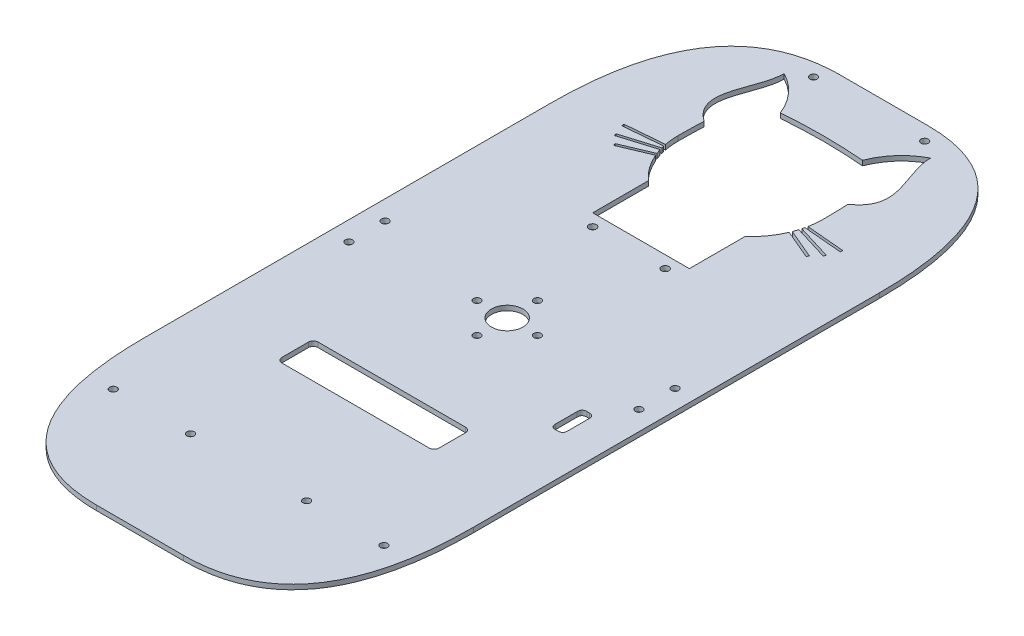
SolidWorks part; units mm, degrees
ref_plane "Спереди" through (0, 0, 0) normal (0, 0, 1) x (1, 0, 0)
ref_plane "Сверху" through (0, 0, 0) normal (0, 1, 0) x (1, 0, 0)
ref_plane "Справа" through (0, 0, 0) normal (1, 0, 0) x (0, 0, -1)
sketch "Эскиз1" plane through (0, 0, 0) normal (0, 1, 0) x (1, 0, 0)
  line L0 (0, 143) -> (0, -165) construction
  line L1 (-68, 143) -> (68, 143)
  line L2 (-68, 143) -> (-68, -165)
  line L3 (-68, -165) -> (68, -165)
  line L4 (68, 143) -> (68, -165)
  line L5 (-68, 0) -> (68, 0) construction
  dimension "D1" = 136
  dimension "D2" = 143
  dimension "D3" = 165
extrude "тело" add sketch "Эскиз1" along normal blind 2
sketch "Эскиз12" plane through (0, 2, 0) normal (0, 1, 0) x (1, 0, 0)
  line L0 (0, 143) -> (0, -165) construction
  line L1 (68, 143) -> (-68, 143) construction
  line L2 (-68, -165) -> (68, -165) construction
  line L3 (60, -3.5) -> (60, -18.5) construction
  line L4 (60, -11) -> (-60, -11) construction
  line L5 (-60, -3.5) -> (-60, -18.5) construction
  circle A0 centre (60, -3.5) radius 1.5
  circle A1 centre (-60, -3.5) radius 1.5
  circle A2 centre (-60, -18.5) radius 1.5
  circle A3 centre (60, -18.5) radius 1.5
  point P12 (-60, -11)
  point P17 (0, -11)
  point P19 (0, -11)
  dimension "D2" = 3
  dimension "D1" = 15
  dimension "D3" = 60
extrude "крепление подвески" cut sketch "Эскиз12" against normal through all
sketch "Эскиз8" plane through (0, 2, 0) normal (0, 1, 0) x (1, 0, 0)
  line L0 (-20, -130) -> (20, -130) construction
  line L1 (0, -165) -> (0, 143) construction
  line L2 (-68, -165) -> (68, -165) construction
  line L3 (68, 143) -> (-68, 143) construction
  circle A0 centre (-20, -130) radius 1.5
  circle A1 centre (20, -130) radius 1.5
  point P10 (0, -130)
  dimension "D1" = 3
  dimension "D2" = 40
  dimension "D3" = 130
extrude "крепление камеры" [suppressed] cut sketch "Эскиз8" against normal through all and the other way through all
sketch "Эскиз13" plane through (0, 2, 0) normal (0, 1, 0) x (1, 0, 0)
  line L0 (0, 143) -> (0, -165) construction
  line L1 (68, 143) -> (-68, 143) construction
  line L2 (-68, -165) -> (68, -165) construction
  line L3 (-57, 99) -> (57, 99) construction
  line L4 (-68, -11) -> (68, -11) construction
  line L5 (-57, -36) -> (57, -36) construction
  line L6 (-68, 143) -> (-68, -165) construction
  line L7 (-57, -111) -> (57, -111) construction
  line L8 (68, -165) -> (68, 143) construction
  line L9 (-25, 99) -> (-57, 99) construction
  line L10 (25, 99) -> (57, 99) construction
  line L11 (-57, -36) -> (-25, -36) construction
  line L12 (25, -36) -> (57, -36) construction
  line L13 (-57, -111) -> (-25, -111) construction
  line L14 (25, -111) -> (57, -111) construction
  circle A0 centre (-57, 99) radius 1.5
  circle A1 centre (57, 99) radius 1.5
  circle A2 centre (57, -36) radius 1.5
  circle A3 centre (-57, -36) radius 1.5
  circle A4 centre (-57, -111) radius 1.5
  circle A5 centre (57, -111) radius 1.5
  circle A6 centre (-25, 99) radius 1.5
  circle A7 centre (25, 99) radius 1.5
  circle A8 centre (25, -36) radius 1.5
  circle A9 centre (-25, -36) radius 1.5
  circle A10 centre (-25, -111) radius 1.5
  circle A11 centre (25, -111) radius 1.5
  point P18 (0, 99)
  point P19 (0, -36)
  point P20 (0, -111)
  point P27 (0, -11)
  dimension "D1" = 3
  dimension "D2" = 110
  dimension "D3" = 25
  dimension "D4" = 100
  dimension "D5" = 114
  dimension "D6" = 32
  dimension "D7" = 32
  dimension "D8" = 32
  dimension "D9" = 32
  dimension "D10" = 32
  dimension "D11" = 32
extrude "крепления уголков" [suppressed] cut sketch "Эскиз13" against normal through all
sketch "Эскиз9" plane through (0, 2, 0) normal (0, 1, 0) x (1, 0, 0)
  line L0 (0, -50) -> (0, 50) construction
  line L2 (-68, -165) -> (68, -165) construction
  circle A0 centre (0, -13) radius 6.5
  circle A1 centre (0, -13) radius 12.5 construction
  circle A2 centre (0, -0.5) radius 1.5
  circle A3 centre (12.5, -13) radius 1.5
  circle A4 centre (-12.5, -13) radius 1.5
  circle A5 centre (0, -25.5) radius 1.5
  dimension "D2" = 13
  dimension "D3" = 25
  dimension "D4" = 3
  dimension "D1" = 152
extrude "ось вращения качалки" cut sketch "Эскиз9" against normal through all
sketch "Эскиз5" plane through (0, 2, 0) normal (0, 1, 0) x (1, 0, 0)
  line L0 (-50, -100) -> (50, -60) construction
  line L1 (-50, -60) -> (50, -60) construction
  line L2 (-50, -60) -> (-50, -100) construction
  line L3 (-50, -100) -> (50, -100) construction
  line L4 (50, -60) -> (50, -100) construction
  line L5 (-50, -60) -> (50, -100) construction
  line L6 (-68, -165) -> (68, -165) construction
  circle A0 centre (-50, -60) radius 1.5
  circle A1 centre (50, -60) radius 1.5
  circle A2 centre (50, -100) radius 1.5
  circle A3 centre (-50, -100) radius 1.5
  point P12 (0, -80)
  dimension "D1" = 3
  dimension "D2" = 100
  dimension "D3" = 40
  dimension "D4" = 65
extrude "крепление raspberry" [suppressed] cut sketch "Эскиз5" against normal through all
sketch "Эскиз11" plane through (0, 2, 0) normal (0, 1, 0) x (1, 0, 0)
  line L0 (-32.5, -68.2307) -> (32.5, -68.2307) construction
  line L1 (-32.5, -60.7307) -> (32.5, -60.7307)
  line L2 (-32.5, -60.7307) -> (-32.5, -75.7307)
  line L3 (-32.5, -75.7307) -> (32.5, -75.7307)
  line L4 (32.5, -60.7307) -> (32.5, -75.7307)
  point P11 (0, -60.7307)
  dimension "D1" = 65
  dimension "D2" = 15
extrude "отверстие под провода на нижний этаж" cut sketch "Эскиз11" against normal through all
fillet "Скругление3" radius 2 4 edges at (-32.5, 1, 75.7307) (32.5, 1, 75.7307) (32.5, 1, 60.7307) (-32.5, 1, 60.7307)
sketch "Эскиз14" [suppressed] plane through (0, 2, 0) normal (0, 1, 0) x (1, 0, 0)
  line L0 (0, 160) -> (0, -130) construction
  line L1 (68, 160) -> (-68, 160) construction
  line L2 (-68, -130) -> (68, -130) construction
  line L3 (-47.5, -125) -> (47.5, -125) construction
  line L4 (47.5, -115) -> (47.5, -135) construction
  line L5 (-12.5, -95) -> (12.5, -95) construction
  line L6 (-47.5, -115) -> (-47.5, -135) construction
  circle A0 centre (-47.5, -115) radius 1.5
  circle A1 centre (-47.5, -135) radius 1.5
  circle A2 centre (47.5, -115) radius 1.5
  circle A3 centre (47.5, -135) radius 1.5
  point P8 (0, -125)
  point P14 (-47.5, -125)
  point P15 (47.5, -125)
  dimension "D1" = 3
  dimension "D2" = 20
  dimension "D3" = 30
  dimension "D4" = 95
extrude "крепление стопоров" [suppressed] cut sketch "Эскиз14" against normal through all
sketch "Эскиз15" plane through (0, 2, 0) normal (0, 1, 0) x (1, 0, 0)
  line L0 (-23, 136.75) -> (23, 136.75) construction
  line L1 (68, 143) -> (-68, 143) construction
  circle A0 centre (23, 136.75) radius 1.5
  circle A1 centre (-23, 136.75) radius 1.5
  point P6 (0, 136.75)
  dimension "D1" = 3
  dimension "D2" = 6.25
  dimension "D3" = 46
extrude "Крепление фронтальной камеры" cut sketch "Эскиз15" against normal up to next
sketch "Эскиз16" plane through (0, 2, 0) normal (0, 1, 0) x (1, 0, 0)
  line L0 (-56, -120) -> (-24, -120) construction
  line L1 (-68, -165) -> (68, -165) construction
  line L2 (-68, 143) -> (-68, -165) construction
  line L3 (0, -165) -> (0, 143) construction
  line L4 (68, 143) -> (-68, 143) construction
  circle A0 centre (-56, -120) radius 1.5
  circle A1 centre (-24, -120) radius 1.5
  circle A2 centre (24, -120) radius 1.5
  circle A3 centre (56, -120) radius 1.5
  dimension "D1" = 32
  dimension "D4" = 3
  dimension "D2" = 45
  dimension "D3" = 12
extrude "Крепление силовых уголков со стороны буллета" cut sketch "Эскиз16" against normal up to next
sketch "Эскиз17" plane through (0, 2, 0) normal (0, 1, 0) x (1, 0, 0)
  line L1 (48, -30) -> (53, -30)
  line L2 (48, -30) -> (48, -43)
  line L3 (48, -43) -> (53, -43)
  line L4 (53, -30) -> (53, -43)
  dimension "D2" = 13
  dimension "D3" = 5
extrude "Отверстие по дпитание сервоприводов и шилда" cut sketch "Эскиз17" against normal up to next
sketch "Эскиз18" plane through (0, 2, 0) normal (0, 1, 0) x (1, 0, 0)
  line L0 (0, 0) -> (0, 143) construction
  line L1 (68, 143) -> (-68, 143) construction
  line L2 (-20, 42.3884) -> (20, 42.3884)
  line L3 (20, 42.3884) -> (20, 65.3884)
  line L5 (-20, 65.3884) -> (-20, 42.3884)
  line L6 (10, 42.3884) -> (10, 27.3884)
  line L7 (10, 27.3884) -> (-10, 27.3884)
  line L8 (-10, 27.3884) -> (-10, 42.3884)
  line L9 (28.2843, 77.7491) -> (-28.2843, 77.7491)
  line L11 (-29.2321, 81.0049) -> (-45.2082, 79.623)
  line L12 (15, 37.3884) -> (-15, 37.3884) construction
  line L13 (-28.6978, 79.0063) -> (-43.2061, 74.5863)
  line L16 (-27.6267, 76.0544) -> (-39.8248, 70.8909)
  line L17 (-29.4421, 81.9904) -> (-45.2944, 80.6193)
  line L18 (-28.9733, 79.9677) -> (-43.4975, 75.5429)
  line L19 (-28.0012, 76.9818) -> (-40.2146, 71.8117)
  line L20 (-45.2944, 80.6193) -> (-45.2082, 79.623)
  line L21 (-43.4975, 75.5429) -> (-43.2061, 74.5863)
  line L22 (-40.2146, 71.8117) -> (-39.8248, 70.8909)
  line L23 (-29.3183, 82.0011) -> (-45.2944, 80.6193) construction
  line L24 (-28.6818, 79.0111) -> (-43.2061, 74.5863) construction
  line L25 (-27.6114, 76.0609) -> (-39.8248, 70.8909) construction
  line L26 (40.2146, 71.8117) -> (39.8248, 70.8909)
  line L27 (43.4975, 75.5429) -> (43.2061, 74.5863)
  line L28 (45.2944, 80.6193) -> (45.2082, 79.623)
  line L29 (28.0012, 76.9818) -> (40.2146, 71.8117)
  line L30 (28.9733, 79.9677) -> (43.4975, 75.5429)
  line L31 (29.4421, 81.9904) -> (45.2944, 80.6193)
  line L32 (27.6267, 76.0544) -> (39.8248, 70.8909)
  line L33 (28.6978, 79.0063) -> (43.2061, 74.5863)
  line L34 (29.2321, 81.0049) -> (45.2082, 79.623)
  arc A0 (20, 65.3884) -> (-20, 65.3884) centre (0, 87.7491) ccw construction
  circle A1 centre (15, 37.3884) radius 1.55
  circle A2 centre (-15, 37.3884) radius 1.55
  arc A4 (-30, 87.7491) -> (-28.2843, 115.7491) centre (199.3322, 87.7491) cw
  arc A5 (-28.2843, 115.7491) -> (28.2843, 115.7491) centre (0, -83.2509) cw
  arc A6 (28.2843, 115.7491) -> (30, 87.7491) centre (-199.3322, 87.7491) cw
  arc A7 (-20, 65.3884) -> (-27.6267, 76.0544) centre (0, 87.7491) cw
  arc A8 (20, 65.3884) -> (27.6267, 76.0544) centre (0, 87.7491) ccw
  arc A9 (29.4421, 81.9904) -> (30, 87.7491) centre (0, 87.7491) ccw
  arc A10 (-30.2864, 131.9093) -> (-16.9975, 117.0291) centre (-43.1419, 107.0545) cw
  arc A11 (30.2864, 131.9093) -> (16.9975, 117.0291) centre (43.1419, 107.0545) ccw
  arc A12 (28.9733, 79.9677) -> (29.2321, 81.0049) centre (0, 87.7491) ccw
  arc A13 (28.0012, 76.9818) -> (28.6978, 79.0063) centre (0, 87.7491) ccw
  arc A14 (-28.0012, 76.9818) -> (-28.6978, 79.0063) centre (0, 87.7491) cw
  arc A15 (-28.9733, 79.9677) -> (-29.2321, 81.0049) centre (0, 87.7491) cw
  arc A16 (-29.4421, 81.9904) -> (-30, 87.7491) centre (0, 87.7491) cw
  spline S0 degree 3 poles (-29.7583, 98.2745) (-43.0929, 107.4905) (-30.2542, 120.6232) (-30.2864, 131.9093) knots 0 0 0 0 1 1 1 1
  spline S1 degree 3 poles (29.7583, 98.2745) (43.0929, 107.4905) (30.2542, 120.6232) (30.2864, 131.9093) knots 0 0 0 0 1 1 1 1
  point P9 (0, 27.3884)
  point P15 (0, 42.3884)
  point P25 (0, 37.3884)
  dimension "D6" = 60
  dimension "D8" = 3.1
  dimension "D1" = 40
  dimension "D2" = 20
  dimension "D3" = 15
  dimension "D4" = 23
  dimension "D5" = 10
  dimension "D7" = 12
  dimension "D9" = 5
  dimension "D10" = 30
  dimension "D11" = 38
  dimension "D12" = 56.5685
  dimension "D16" = 6
  dimension "D13" = 1
  dimension "D14" = 1
  dimension "D15" = 1
fillet "Скругление4" radius 50 2 edges at (68, 1, 165) (-68, 1, -143) second distance 70 conic rho 0.5 first distance on face at (0, 1, 165) first distance on face at (0, 1, -143)
fillet "Скругление5" radius 70 2 edges at (-68, 1, 165) (68, 1, -143) second distance 50 conic rho 0.5 first distance on face at (-68, 1.25, -13.5) first distance on face at (68, 1.25, 35.5)
fillet "Скругление6" radius 2 4 edges at (48, 1, 43) (53, 1, 43) (48, 1, 30) (53, 1, 30) conic rho 0.5
sketch "Эскиз19" plane through (0, 2, 0) normal (0, 1, 0) x (1, 0, 0)
  line L1 (-95.3857, 162.9355) -> (76.7354, 162.9355)
  line L2 (-95.3857, 162.9355) -> (-95.3857, 1.5)
  line L3 (-95.3857, 1.5) -> (76.7354, 1.5)
  line L4 (76.7354, 162.9355) -> (76.7354, 1.5)
  circle A0 centre (-60, -3.5) radius 1.5 construction
  dimension "D1" = 5
extrude "Вырез-Вытянуть3" [suppressed] cut sketch "Эскиз19" against normal up to next
fillet "Скругление8" [suppressed] radius 10
extrude "Вырез под манипулятор" cut sketch "Эскиз18" against normal up to next contours S0 A4 A5 A10 | A6 S1 A11 A5 | A16 L17 L20 L11 A15 L18 L21 L13 A14 L9 A13 L33 L27 L30 A12 L34 L28 L31 A9 A6 A5 A4 | A14 L19 L22 L16 A7 L5 L2 L3 A8 L32 L26 L29 A13 L9 | A1 | A2 region at (0, 2, -61.3278) region at (0, 2, -96.8323) region at (-28.5376, 2, -116.8678) region at (28.5376, 2, -116.8678) region at (15, 2, -37.3884) region at (-15, 2, -37.3884)
